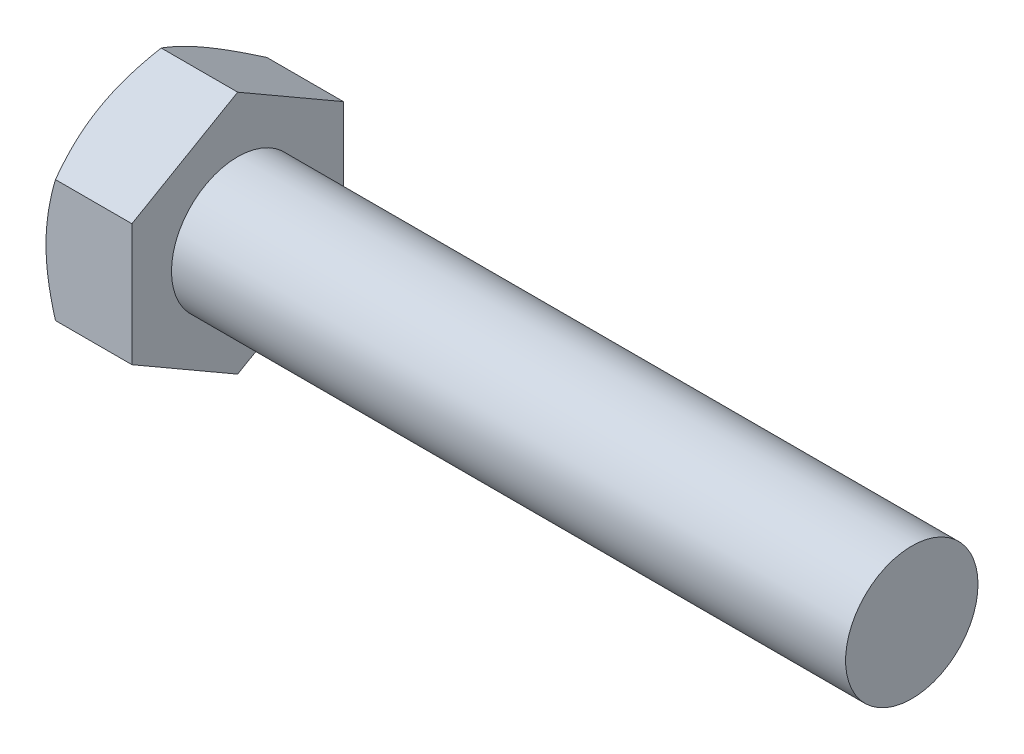
SolidWorks part; units mm, degrees
material "AISI 1020"
ref_plane "Front Plane" through (0, 0, 0) normal (0, 0, 1) x (1, 0, 0)
ref_plane "Top Plane" through (0, 0, 0) normal (0, 1, 0) x (1, 0, 0)
ref_plane "Right Plane" through (0, 0, 0) normal (1, 0, 0) x (0, 0, -1)
sketch "Sketch1" plane through (0, 0, 0) normal (0, 0, 1) x (1, 0, 0)
  line L0 (-22.8203, 0) -> (22.8203, 0) construction
  line L1 (22.8203, 3.9751) -> (22.8203, -3.9751) construction
  line L2 (-17.6609, 6.35) -> (-17.6609, -6.35) construction
  line L3 (-22.8203, 6.35) -> (-22.8203, -6.35) construction
  point P9 (-17.6609, 0)
  point P10 (19.1161, -3.9751)
  point P11 (9.3266, 0)
  dimension "D1" = 3.7042
ref_plane "Plane2" through (22.8203, 0, 0) normal (1, 0, 0) x (0, 0, -1)
sketch "Sketch5" plane through (22.8203, 0, 0) normal (1, 0, 0) x (0, 0, -1)
  circle A0 centre (0, 0) radius 3.9751
extrude "Boss-Extrude3" add sketch "Sketch5" against normal up to vertex (40.4813 mm away) up to point (-17.6609, 0, 0)
sketch "Sketch6" plane through (-17.6609, 0, 0) normal (-1, 0, 0) x (0, 0, 1)
  line L0 (0, 6.35) -> (0, -6.35) construction
  line L1 (6.35, 3.6662) -> (0, 7.3323)
  line L2 (0, 7.3323) -> (-6.35, 3.6662)
  line L3 (-6.35, 3.6662) -> (-6.35, -3.6662)
  line L4 (-6.35, -3.6662) -> (0, -7.3323)
  line L5 (0, -7.3323) -> (6.35, -3.6662)
  line L6 (6.35, -3.6662) -> (6.35, 3.6662)
  circle A0 centre (0, 0) radius 6.35 construction
extrude "Boss-Extrude4" add sketch "Sketch6" along normal up to vertex (5.1594 mm away) up to point (-22.8203, -6.35, 0)
sketch "Sketch7" plane through (-22.8203, 0, 0) normal (-1, 0, 0) x (0, 0, 1)
  circle A0 centre (0, 0) radius 6.35 construction
  circle A1 centre (0, 0) radius 6.35
sketch "Sketch12" plane through (-22.8203, 0, 0) normal (-1, 0, 0) x (0, 0, 1)
  line L0 (0, 4.8895) -> (0, 2.7305) construction
  line L1 (0.1905, 4.8895) -> (0.1905, 2.7305)
  line L2 (-0.1905, 4.8895) -> (-0.1905, 2.7305)
  line L3 (0, 3.9751) -> (0, -3.9751) construction
  arc A0 (0.1905, 4.8895) -> (-0.1905, 4.8895) centre (0, 4.8895) ccw
  arc A1 (-0.1905, 2.7305) -> (0.1905, 2.7305) centre (0, 2.7305) ccw
  circle A3 centre (0, 0) radius 2.54 construction
  circle A4 centre (0, 0) radius 5.08 construction
  point P2 (0, 3.81)
  dimension "D3" = 10.16
  dimension "D2" = 0.381
sketch "Sketch8" plane through (-22.8203, 0, 0) normal (-1, 0, 0) x (0, 0, 1)
  circle A0 centre (0, 0) radius 6.35 construction
  circle A1 centre (0, 0) radius 6.35
extrude "Cut-Extrude3" cut sketch "Sketch8" against normal through all draft 60 flip side to cut
ref_plane "Split Plane" through (9.3266, 0, 0) normal (1, 0, 0) x (0, 0, -1)
ref_axis "Center Axis 1" through (-22.8203, 0, 0) along (1, 0, 0)
ref_plane "Contact Plane 1" through (-17.6609, 0, 0) normal (1, 0, 0) x (0, 0, -1)
split "Split1" [suppressed] bodies to split 113
sketch "Sketch9" [suppressed] plane through (22.8203, 0, 0) normal (1, 0, 0) x (0, 0, -1)
  circle A1 centre (0, 0) radius 3.9751
  circle A2 centre (0, 0) radius 3.9751
  dimension "D1" = 0
curve "Helix/Spiral1" [suppressed] pitch 1.0583 height 14.5521 turns 13.75 parameters "Pitch"=1.0583
chamfer "Chamfer1" [suppressed] distance 0.7938 angle 45
sketch "Sketch10" [suppressed] plane through (0, 0, 0) normal (0, 0, 1) x (1, 0, 0)
  line L0 (22.8203, 3.9751) -> (23.2172, 3.2877)
  line L1 (23.2172, 3.2877) -> (23.3495, 3.2877)
  line L2 (23.3495, 3.2877) -> (23.7464, 3.9751)
  line L3 (22.8203, 3.9751) -> (23.7464, 3.9751)
  line L4 (23.2833, 3.9751) -> (23.2833, 3.2877) construction
  line L5 (23.0188, 3.6314) -> (23.5479, 3.6314) construction
  dimension "D1" = 60
  dimension "D2" = 0.1323
  dimension "D3" = 0.5292
sweep "Cut-Sweep1" [suppressed] cut profiles "Sketch10" path "Helix/Spiral1"
sketch "Sketch15" [suppressed] plane through (9.3266, 0, 0) normal (1, 0, 0) x (0, 0, -1)
  circle A0 centre (0, 0) radius 3.9751 construction
  circle A1 centre (0, 0) radius 3.9751
extrude "Boss-Extrude5" [suppressed] add sketch "Sketch15" along normal through all draft 40
equation "\"D2@Sketch10\" = \"Pitch@Helix/Spiral1\"*.125"
equation "\"D3@Sketch10\" = \"Pitch@Helix/Spiral1\"*.5"
equation "\"D3@Helix/Spiral1\"=\"Min Thread@Sketch1\"+\"Pitch@Helix/Spiral1\""
equation "\"D1@Chamfer1\" = \"Pitch@Helix/Spiral1\"*.75"
equation "\"D1@Sketch12\" = \"Hex@Sketch1\"*.4"
equation "\"D3@Sketch12\" = \"Hex@Sketch1\"*.8"
equation "\"D2@Sketch12\" = \"Hex@Sketch1\"*.03"
equation "\"D1@Sketch1\" = \"Pitch@Helix/Spiral1\"*3.5"
